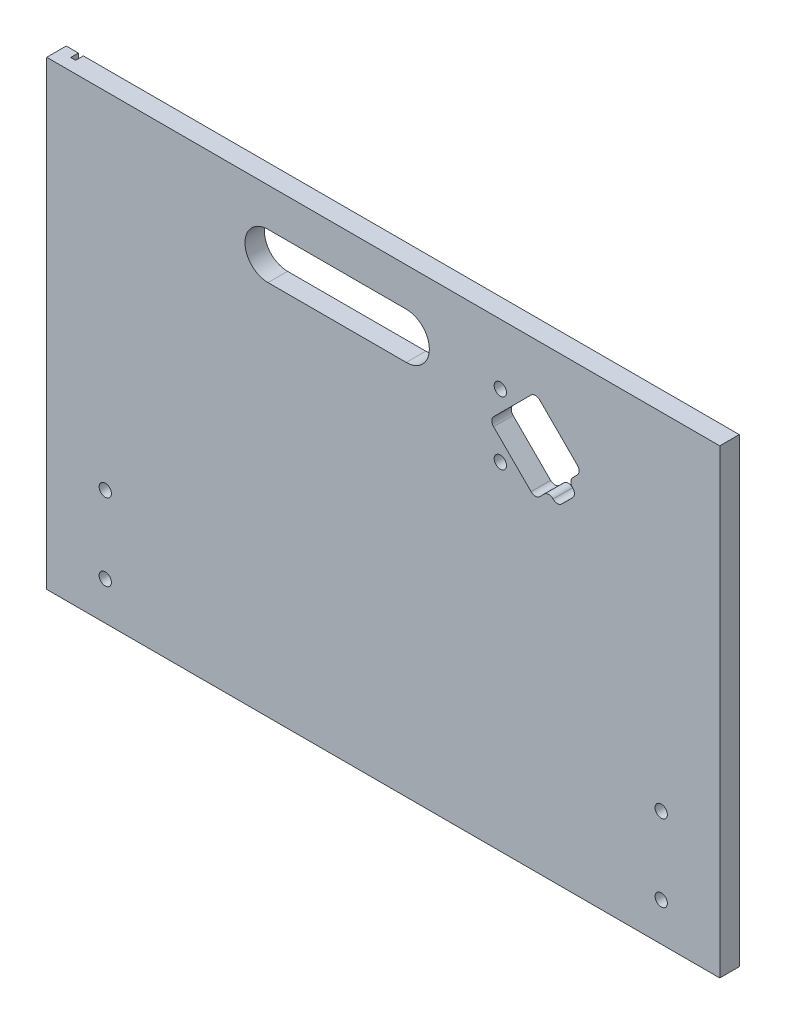
SolidWorks part; units mm, degrees
ref_plane "Front Plane" through (0, 0, 0) normal (0, 0, 1) x (1, 0, 0)
ref_plane "Top Plane" through (0, 0, 0) normal (0, 1, 0) x (1, 0, 0)
ref_plane "Right Plane" through (0, 0, 0) normal (1, 0, 0) x (0, 0, -1)
sketch "Sketch1" plane through (0, 0, 0) normal (0, 0, 1) x (1, 0, 0)
  line L1 (219.05, -150) -> (-219.05, -150)
  line L2 (219.05, -150) -> (219.05, 150) construction
  line L3 (219.05, 150) -> (-219.05, 150)
  line L4 (-219.05, -150) -> (-219.05, 150) construction
  line L5 (219.05, -150) -> (-219.05, 150) construction
  line L6 (219.05, 150) -> (-219.05, -150) construction
  line L8 (0, 150) -> (0, -150) construction
  line L11 (-219.05, 150) -> (-219.05, -150)
  line L12 (219.05, 150) -> (219.05, -150)
  point P0 (0, 0)
  dimension "D1" = 438.1
  dimension "D4350" = 300
extrude "Boss-Extrude1" add sketch "Sketch1" along normal blind 12.7 contours L12 L3 L11 L1 region at (0, 0, 0)
sketch "Sketch2" plane through (0, 0, 12.7) normal (0, 0, 1) x (1, 0, 0)
  line L0 (99.05, 150) -> (99.05, -150) construction
  line L1 (219.05, 150) -> (-219.05, 150) construction
  line L2 (219.05, -150) -> (-219.05, -150) construction
  line L3 (219.05, 150) -> (219.05, -150) construction
  line L4 (219.05, 90) -> (-219.05, 90) construction
  line L5 (-219.05, 150) -> (-219.05, -150) construction
  circle A0 centre (76.2149, 110.5901) radius 4
  line B0 (99.05, 111.9118) -> (99.05, 68.0882) construction
  line B1 (84.024, 105.026) -> (114.076, 74.974) construction
  line B2 (99.05, 120.052) -> (68.998, 90)
  line B3 (99.05, 120.052) -> (129.102, 90)
  line B4 (129.102, 90) -> (99.05, 59.948) construction
  line B5 (68.998, 90) -> (99.05, 59.948)
  line B6 (99.05, 120.052) -> (99.05, 59.948) construction
  line B7 (129.102, 90) -> (68.998, 90) construction
  line B8 (120.44, 81.3379) -> (126.0968, 75.6811)
  line B9 (114.076, 74.974) -> (119.7329, 69.3171) construction
  line B10 (126.0968, 75.6811) -> (113.3689, 62.9532)
  line B11 (107.7121, 68.61) -> (113.3689, 62.9532)
  line B12 (129.102, 90) -> (120.44, 81.3379)
  line B13 (99.05, 59.948) -> (107.7121, 68.61)
  circle B14 centre (76.2149, 110.5901) radius 4
  circle B15 centre (76.2149, 69.4099) radius 4
  line B16 (74.7026, 94.9282) -> (94.1218, 114.3474) construction
  line B17 (103.9782, 114.3474) -> (123.3974, 94.9282) construction
  line B18 (123.3974, 85.0718) -> (103.9782, 65.6526) construction
  line B19 (94.1218, 65.6526) -> (74.7026, 85.0718) construction
  circle B20 centre (120.9618, 90) radius 1.5541 construction
  arc B21 (74.7026, 85.0718) -> (74.7026, 94.9282) centre (99.05, 90) cw construction
  arc B22 (94.1218, 114.3474) -> (103.9782, 114.3474) centre (99.05, 90) cw construction
  arc B23 (123.3974, 94.9282) -> (123.3974, 85.0718) centre (99.05, 90) cw construction
  arc B24 (103.9782, 65.6526) -> (94.1218, 65.6526) centre (99.05, 90) cw construction
  circle B25 centre (99.05, 90) radius 13.462 construction
  circle B26 centre (99.05, 68.0882) radius 1.5541 construction
  circle B27 centre (77.1382, 90) radius 1.5541 construction
  circle B28 centre (99.05, 111.9118) radius 1.5541 construction
  line B29 (101.2951, 121.9435) -> (96.8049, 117.4534) construction
  line B30 (96.8049, 117.4534) -> (128.7485, 85.5099) construction
  line B31 (128.7485, 94.4901) -> (101.2951, 121.9435) construction
  line B32 (128.7485, 94.4901) -> (96.8049, 62.5466) construction
  line B33 (96.8049, 62.5466) -> (101.2951, 58.0565) construction
  line B34 (101.2951, 58.0565) -> (128.7485, 85.5099) construction
  line B35 (96.8049, 117.4534) -> (69.3515, 117.4534) construction
  line B36 (69.3515, 117.4534) -> (69.3515, 62.5466) construction
  line B37 (96.8049, 62.5466) -> (69.3515, 62.5466) construction
  circle B38 centre (76.2149, 69.4099) radius 4 construction
  circle B39 centre (76.2149, 110.5901) radius 4 construction
  circle B40 centre (99.05, 90) radius 13.462 construction
  circle B41 centre (99.05, 111.9118) radius 1.5541 construction
  circle B42 centre (120.9618, 90) radius 1.5541 construction
  circle B43 centre (99.05, 68.0882) radius 1.5541 construction
  circle B44 centre (77.1382, 90) radius 1.5541 construction
  dimension "D1" = 120
  dimension "D2" = 60
sketch_block_instance "Block1-2"
sketch_block "Block1" parameters "D1"=42.5, "D2"=8, "D3"=18
sketch_block_instance "nema 17 mount dxf-1"
sketch_block "nema 17 mount dxf"
sketch_block_instance "Fold pattern - Angle Mount v3-1"
sketch_block "Fold pattern - Angle Mount v3"
extrude "Cut-Extrude1" cut sketch "Sketch2" against normal up to next contours B3 B2 B5 B13 B11 B10 B8 B12 | A0 | B15 region at (76.2149, 110.5901, 12.7) region at (100.3683, 88.6817, 12.7) region at (76.2149, 69.4099, 12.7)
fillet "Fillet1" radius 4 8 edges at (99.05, 120.052, 6.35) (68.998, 90, 6.35) (120.44, 81.3379, 6.35) (126.0968, 75.6811, 6.35) (113.3689, 62.9532, 6.35) (107.7121, 68.61, 6.35) (99.05, 59.948, 6.35) (129.102, 90, 6.35)
sketch "Sketch3" plane through (0, 0, 0) normal (0, 0, -1) x (-1, 0, 0)
  line L1 (-219.05, 150) -> (219.05, 150) construction
  line L2 (207.9375, 150) -> (211.1125, 150)
  line L3 (207.9375, 150) -> (207.9375, -55)
  line L4 (207.9375, -55) -> (211.1125, -55)
  line L6 (211.1125, 150) -> (211.1125, -55)
  line L7 (209.525, 150) -> (209.525, -55) construction
  line L8 (219.05, 150) -> (219.05, -150) construction
  line L9 (-219.05, -150) -> (219.05, -150) construction
  dimension "D1" = 3.175
  dimension "D2" = 9.525
  dimension "D3" = 95
extrude "Cut-Extrude2" cut sketch "Sketch3" against normal blind 5
sketch "Sketch4" plane through (0, 0, 0) normal (0, 0, -1) x (-1, 0, 0)
  line L0 (-219.05, -150) -> (219.05, -150) construction
  line B0 (-219.05, -50) -> (219.05, -50) construction
  line B1 (-206.35, -100) -> (-155.55, -100) construction
  line B2 (-219.05, -50) -> (-206.35, -50) construction
  line B3 (-219.05, -50) -> (-219.05, -150) construction
  line B4 (-219.05, -150) -> (-206.35, -150) construction
  line B5 (-206.35, -50) -> (-206.35, -150) construction
  line B6 (-206.35, -150) -> (-155.55, -150) construction
  line B7 (-206.35, -150) -> (-206.35, -50) construction
  line B8 (-206.35, -50) -> (-155.55, -50) construction
  line B9 (-155.55, -150) -> (-155.55, -50) construction
  line B10 (-180.95, -100) -> (-180.95, -50) construction
  line B11 (0, -50) -> (0, -150) construction
  line B12 (180.95, -100) -> (180.95, -50) construction
  line B13 (155.55, -150) -> (155.55, -50) construction
  line B14 (206.35, -50) -> (155.55, -50) construction
  line B15 (206.35, -150) -> (206.35, -50) construction
  line B16 (206.35, -150) -> (155.55, -150) construction
  line B17 (206.35, -50) -> (206.35, -150) construction
  line B18 (219.05, -150) -> (206.35, -150) construction
  line B19 (219.05, -50) -> (219.05, -150) construction
  line B20 (219.05, -50) -> (206.35, -50) construction
  line B21 (206.35, -100) -> (155.55, -100) construction
  circle B22 centre (-180.95, -75) radius 4
  circle B23 centre (-180.95, -125) radius 4
  circle B24 centre (180.95, -125) radius 4
  circle B25 centre (180.95, -75) radius 4
sketch_block_instance "Block3-1"
sketch_block "Block3" parameters "D1"=8
extrude "Cut-Extrude3" cut sketch "Sketch4" against normal up to next
sketch "Sketch5" plane through (0, 0, 12.7) normal (0, 0, 1) x (1, 0, 0)
  line L0 (219.05, 150) -> (-219.05, 150) construction
  line L5 (15, 110) -> (-75, 110) construction
  line L6 (15, 95) -> (-75, 95)
  line L7 (15, 125) -> (-75, 125)
  arc A0 (71.8264, 92.8284) -> (71.8264, 87.1716) centre (74.6548, 90) ccw construction
  arc A2 (15, 95) -> (15, 125) centre (15, 110) ccw
  arc A3 (-75, 125) -> (-75, 95) centre (-75, 110) ccw
  point P9 (70.6548, 90)
  point P12 (-30, 110)
  dimension "D4" = 15
  dimension "D1" = 90
  dimension "D2" = 30
  dimension "D3" = 40
extrude "Cut-Extrude4" cut sketch "Sketch5" against normal up to next
